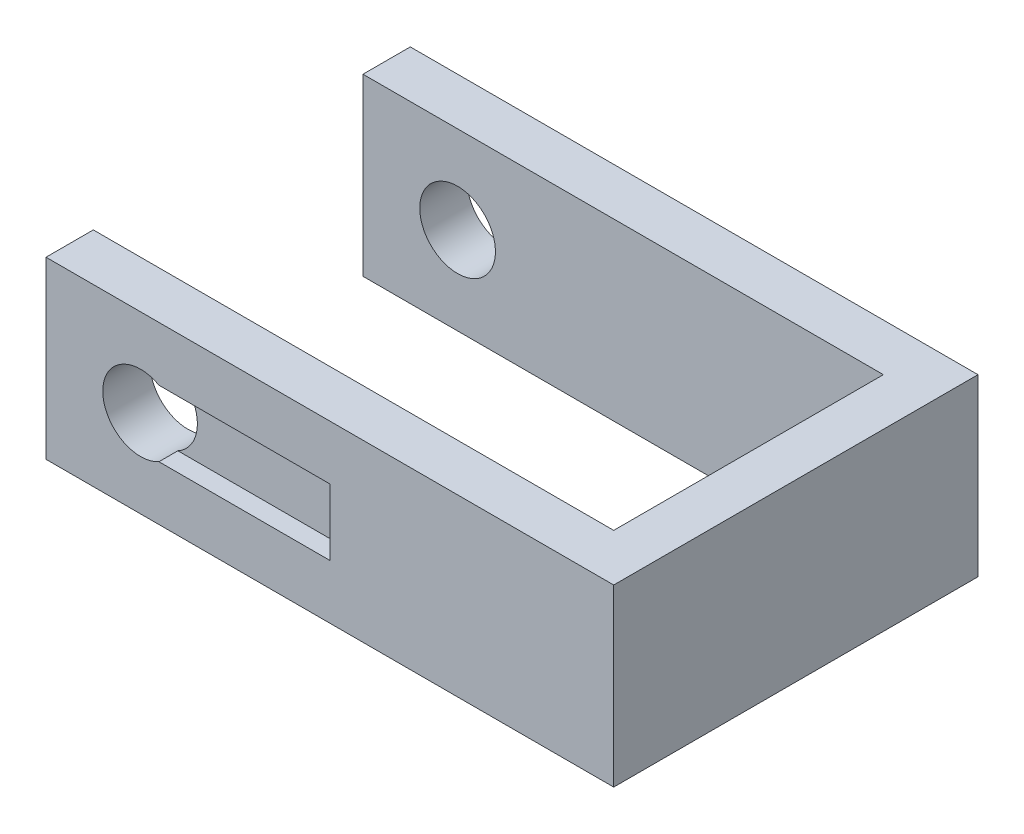
SolidWorks part; units mm, degrees
ref_plane "Front Plane" through (0, 0, 0) normal (0, 0, 1) x (1, 0, 0)
ref_plane "Top Plane" through (0, 0, 0) normal (0, 1, 0) x (1, 0, 0)
ref_plane "Right Plane" through (0, 0, 0) normal (1, 0, 0) x (0, 0, -1)
sketch "Sketch1" plane through (0, 0, 0) normal (0, 1, 0) x (1, 0, 0)
  line L0 (-2.5, 14.25) -> (-2.5, -0.75)
  line L1 (2.5, -14.25) -> (-2.5, -14.25)
  line L2 (2.5, -14.25) -> (2.5, 14.25)
  line L3 (2.5, 14.25) -> (-2.5, 14.25)
  line L4 (-2.5, -14.25) -> (-2.5, 14.25)
  line L5 (2.5, -14.25) -> (-2.5, 14.25) construction
  line L6 (2.5, 14.25) -> (-2.5, -14.25) construction
  line L7 (2.5, 14.25) -> (-57.5, 14.25)
  line L8 (2.5, 14.25) -> (2.5, 19.25)
  line L9 (-57.5, 14.25) -> (-57.5, 19.25)
  line L10 (0, 0) -> (-57.5, 0) construction
  line L11 (2.5, 19.25) -> (-57.5, 19.25)
  line L12 (2.5, -14.25) -> (2.5, -19.25)
  line L13 (-57.5, -14.25) -> (-57.5, -19.25)
  line L14 (2.5, -19.25) -> (-57.5, -19.25)
  line L15 (2.5, -14.25) -> (-57.5, -14.25)
  line L16 (2.5, 0) -> (-57.5, 0) construction
  point P0 (0, 0)
  dimension "D1" = 28.5
  dimension "D2" = 5
  dimension "D3" = 60
  dimension "D4" = 5
extrude "Boss-Extrude2" add sketch "Sketch1" against normal blind 18.5 contours L1 L15 L13 L14 L12 | L4 L1 L2 L3 L0 | L8 L11 L9 L7 L3 region at (0, 0, 0) region at (-27.5, 0, -16.75) region at (-27.5, 0, 16.75)
sketch "Sketch5" plane through (0, 0, 19.25) normal (0, 0, 1) x (1, 0, 0)
  line L0 (-57.5, -9.25) -> (2.5, -9.25) construction
  line L1 (-57.5, -18.5) -> (-57.5, 0) construction
  line L2 (2.5, -18.5) -> (2.5, 0) construction
  circle A0 centre (-47.5, -9.25) radius 4
  dimension "D1" = 8
  dimension "D2" = 10
extrude "Cut-Extrude3" cut sketch "Sketch5" against normal blind 38.5
sketch "Sketch6" plane through (0, 0, 19.25) normal (0, 0, 1) x (1, 0, 0)
  line L0 (-57.5, -18.5) -> (-57.5, 0) construction
  line L1 (-27.5, -12.75) -> (-47.5, -12.75)
  line L2 (-27.5, -12.75) -> (-27.5, -5.75)
  line L3 (-27.5, -5.75) -> (-47.5, -5.75)
  line L4 (-47.5, -12.75) -> (-47.5, -5.75)
  line L5 (-27.5, -12.75) -> (-47.5, -5.75) construction
  line L6 (-27.5, -5.75) -> (-47.5, -12.75) construction
  circle A0 centre (-47.5, -9.25) radius 4 construction
  point P0 (-37.5, -9.25)
  point P7 (-57.5, -9.25)
  dimension "D1" = 0
  dimension "D2" = 7
  dimension "D3" = 20
  dimension "D4" = 0
extrude "Cut-Extrude4" cut sketch "Sketch6" against normal blind 2
sketch "Sketch8" plane through (0, 0, -19.25) normal (0, 0, -1) x (-1, 0, 0)
  line L0 (47.5, -12.75) -> (27.5, -12.75)
  line L1 (47.5, -12.75) -> (47.5, -5.75)
  line L2 (47.5, -5.75) -> (27.5, -5.75)
  line L3 (27.5, -12.75) -> (27.5, -5.75)
  line L4 (47.5, -12.75) -> (27.5, -5.75) construction
  line L5 (47.5, -5.75) -> (27.5, -12.75) construction
  line L7 (57.5, -18.5) -> (57.5, 0) construction
  circle A0 centre (47.5, -9.25) radius 4 construction
  point P0 (37.5, -9.25)
  point P9 (57.5, -9.25)
  dimension "D1" = 7
  dimension "D2" = 20
  dimension "D3" = 3.5
  dimension "D4" = 0
extrude "Cut-Extrude5" cut sketch "Sketch8" against normal blind 2
